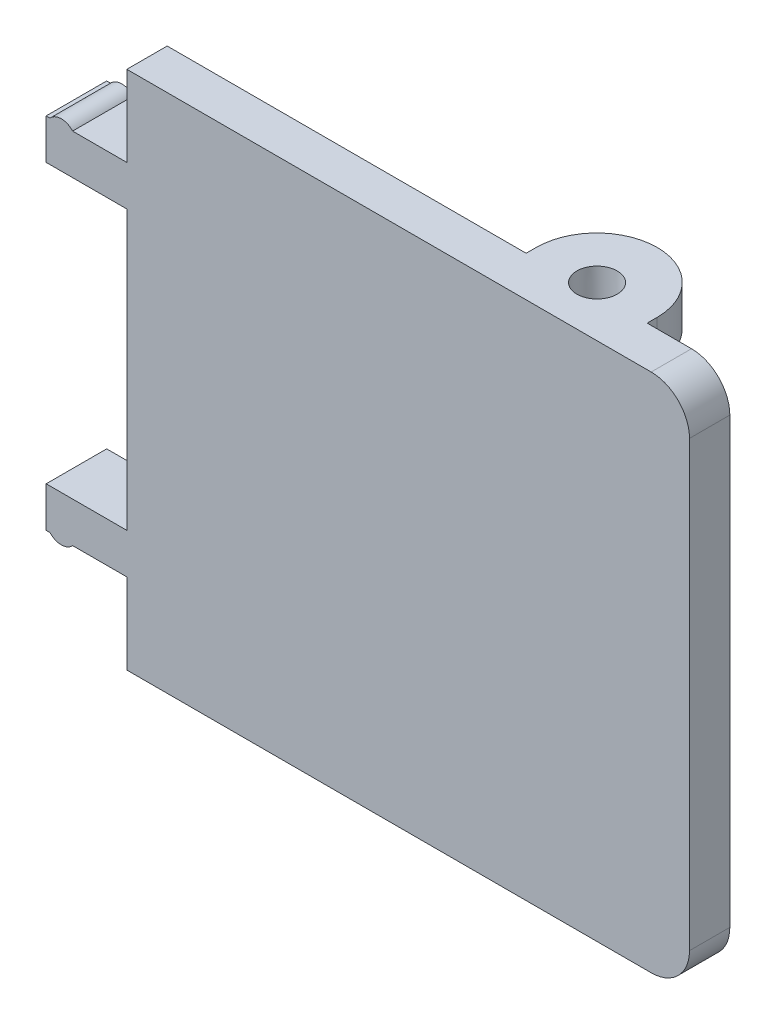
SolidWorks part; units mm, degrees
ref_plane "前视基准面" through (0, 0, 0) normal (0, 0, 1) x (1, 0, 0)
ref_plane "上视基准面" through (0, 0, 0) normal (0, 1, 0) x (1, 0, 0)
ref_plane "右视基准面" through (0, 0, 0) normal (1, 0, 0) x (0, 0, -1)
other "Configuration Table"
sketch "草图1" plane through (0, 0, 0) normal (0, 0, 1) x (1, 0, 0)
  line L3 (-11.9424, 3.3113) -> (-11.9424, -22.4887)
  line L4 (-11.9424, 6.4113) -> (-11.9424, -25.5887) construction
  line L6 (-11.9424, -22.4887) -> (14.0576, -22.4887)
  line L7 (15.9576, -20.5887) -> (15.9576, 1.4113)
  line L8 (14.0576, 3.3113) -> (-11.9424, 3.3113)
  line L9 (-11.9424, -22.4887) -> (14.0576, -22.4887)
  line L10 (15.9576, -20.5887) -> (15.9576, 1.4113)
  line L11 (14.0576, 3.3113) -> (-11.9424, 3.3113)
  arc A4 (14.0576, -22.4887) -> (15.9576, -20.5887) centre (14.0576, -20.5887) ccw
  arc A5 (15.9576, 1.4113) -> (14.0576, 3.3113) centre (14.0576, 1.4113) ccw
  arc A6 (14.0576, -22.4887) -> (15.9576, -20.5887) centre (14.0576, -20.5887) ccw
  arc A7 (15.9576, 1.4113) -> (14.0576, 3.3113) centre (14.0576, 1.4113) ccw
  point P3 (-11.9424, -22.8087)
  dimension "D1" = 0.1
extrude "凸台-拉伸1" add sketch "草图1" against normal blind 2
sketch "草图2" plane through (0, 0, -2) normal (0, 0, -1) x (-1, 0, 0)
  line L0 (11.9424, -22.4887) -> (-14.0576, -22.4887) construction
  line L1 (-5.8576, -22.4887) -> (-11.8576, -22.4887)
  line L2 (-5.8576, -22.4887) -> (-5.8576, -20.4887)
  line L3 (-5.8576, -20.4887) -> (-11.8576, -20.4887)
  line L4 (-11.8576, -22.4887) -> (-11.8576, -20.4887)
  line L5 (-14.0576, 3.3113) -> (11.9424, 3.3113) construction
  line L6 (-5.8576, 3.3113) -> (-11.8576, 3.3113)
  line L7 (-5.8576, 3.3113) -> (-5.8576, 1.3113)
  line L8 (-5.8576, 1.3113) -> (-11.8576, 1.3113)
  line L9 (-11.8576, 3.3113) -> (-11.8576, 1.3113)
  line L10 (-18.0576, -20.5887) -> (-18.0576, 1.4113) construction
  dimension "D1" = 6
  dimension "D2" = 6.2
  dimension "D3" = 2
extrude "凸台-拉伸2" add sketch "草图2" along normal blind 3.5
fillet "圆角1" radius 3 4 edges at (11.8576, 2.3113, -5.5) (5.8576, 2.3113, -5.5) (11.8576, -21.4887, -5.5) (5.8576, -21.4887, -5.5)
sketch "草图3" plane through (0, -22.4887, 0) normal (0, -1, 0) x (1, 0, 0)
  circle A0 centre (8.8741, -2.5) radius 1
  dimension "D1" = 2
extrude "切除-拉伸1" cut sketch "草图3" against normal blind 5 draft 2
sketch "草图4" plane through (0, 3.3113, 0) normal (0, 1, 0) x (1, 0, 0)
  circle A0 centre (8.8741, 2.5) radius 1
  dimension "D1" = 2
extrude "切除-拉伸2" cut sketch "草图4" against normal blind 5 draft 2
sketch "草图6" plane through (0, 0, 0) normal (0, 0, 1) x (1, 0, 0)
  line L0 (-11.9424, 3.3113) -> (-11.9424, -22.4887) construction
  line L1 (-11.9424, -0.6887) -> (-15.9424, -0.6887)
  line L2 (-11.9424, -0.6887) -> (-11.9424, -2.6887)
  line L3 (-11.9424, -2.6887) -> (-15.9424, -2.6887)
  line L4 (-15.9424, -0.6887) -> (-15.9424, -2.6887)
  line L5 (14.0576, 3.3113) -> (-11.9424, 3.3113) construction
  line L6 (-11.9424, -18.4887) -> (-15.9424, -18.4887)
  line L7 (-11.9424, -18.4887) -> (-11.9424, -16.4887)
  line L8 (-11.9424, -16.4887) -> (-15.9424, -16.4887)
  line L9 (-15.9424, -18.4887) -> (-15.9424, -16.4887)
  line L10 (-11.9424, -22.4887) -> (14.0576, -22.4887) construction
  point P14 (0, 0)
  dimension "D1" = 2
  dimension "D2" = 4
  dimension "D3" = 4
  dimension "D4" = 4
extrude "凸台-拉伸3" add sketch "草图6" against normal blind 3
chamfer "倒角1" distance 3 angle 45 2 edges at (-11.9424, -17.4887, -2) (-11.9424, -1.6887, -2)
sketch "草图7" plane through (0, 0, 0) normal (0, 0, 1) x (1, 0, 0)
  line L0 (-15.9424, -0.6887) -> (-15.9424, -2.6887) construction
  line L1 (-15.9424, -2.6887) -> (-11.9424, -2.6887) construction
  line L2 (-15.9424, -16.4887) -> (-15.9424, -18.4887) construction
  line L3 (-11.9424, -16.4887) -> (-15.9424, -16.4887) construction
  circle A0 centre (-15.1924, -1.1887) radius 0.75
  circle A1 centre (-15.1924, -17.9887) radius 0.75
  point P8 (0, 0)
  dimension "D1" = 1.5
  dimension "D3" = 1.5
  dimension "D2" = 1.5
extrude "凸台-拉伸4" add sketch "草图7" against normal blind 3
